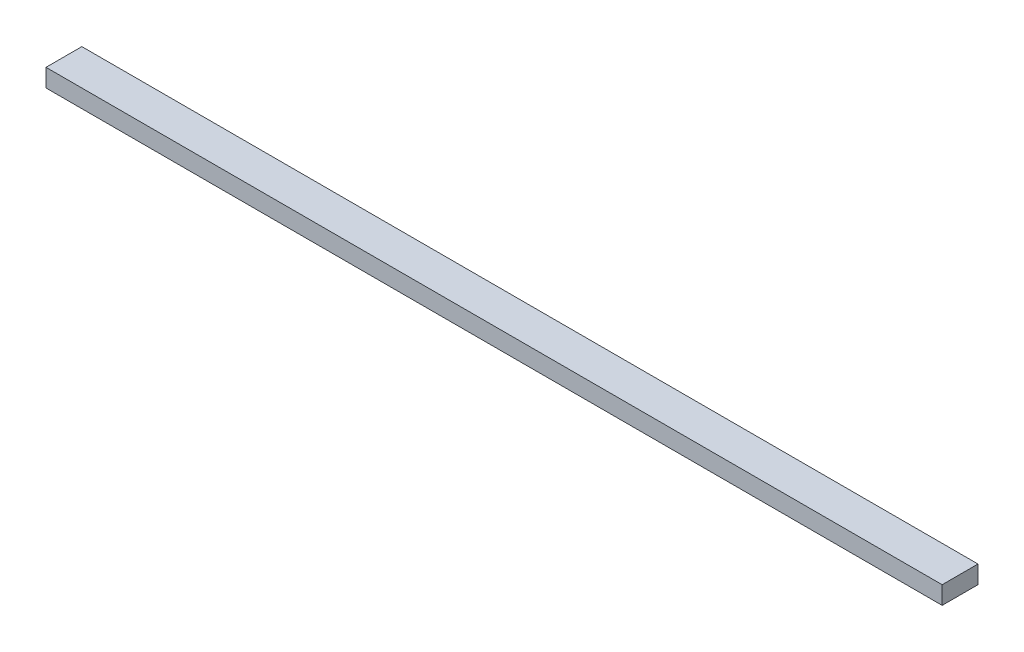
SolidWorks part; units mm, degrees
ref_plane "前视基准面" through (0, 0, 0) normal (0, 0, 1) x (1, 0, 0)
ref_plane "上视基准面" through (0, 0, 0) normal (0, 1, 0) x (1, 0, 0)
ref_plane "右视基准面" through (0, 0, 0) normal (1, 0, 0) x (0, 0, -1)
sketch "草图1" plane through (0, 0, 0) normal (0, 1, 0) x (1, 0, 0)
  line L0 (-106.6888, 0) -> (107.0504, 0) construction
  line L1 (0, 77.9371) -> (0, -83.7236) construction
  line L2 (-92.1101, 6.2176) -> (157.8899, 6.2176)
  line L3 (157.8899, 6.2176) -> (157.8899, -3.7824)
  line L4 (157.8899, -3.7824) -> (-92.1101, -3.7824)
  line L5 (-92.1101, -3.7824) -> (-92.1101, 6.2176)
extrude "凸台-拉伸1" add sketch "草图1" along normal blind 5
